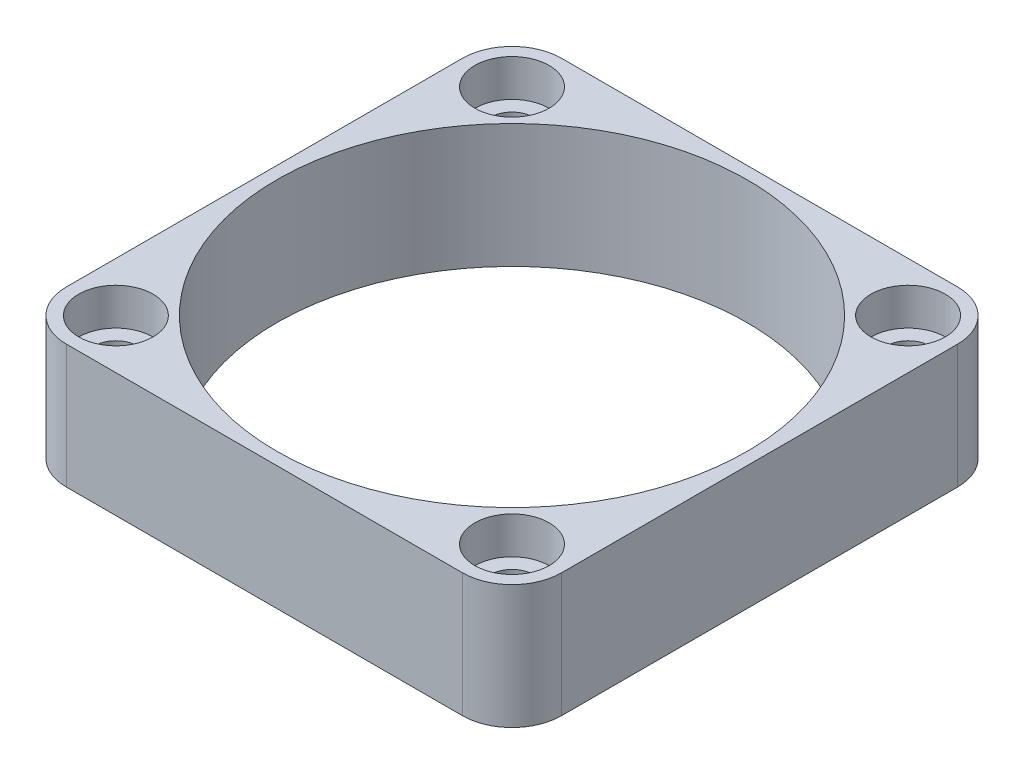
SolidWorks part; units mm, degrees
material "ABS"
ref_plane "Front Plane" through (0, 0, 0) normal (0, 0, 1) x (1, 0, 0)
ref_plane "Top Plane" through (0, 0, 0) normal (0, 1, 0) x (1, 0, 0)
ref_plane "Right Plane" through (0, 0, 0) normal (1, 0, 0) x (0, 0, -1)
sketch "Sketch1" plane through (0, 0, 0) normal (0, 1, 0) x (1, 0, 0)
  line L1 (4, 0) -> (36, 0)
  line L2 (0, 4) -> (0, 36)
  line L3 (4, 40) -> (36, 40)
  line L4 (40, 4) -> (40, 36)
  arc A0 (4, 40) -> (0, 36) centre (4, 36) ccw
  arc A1 (0, 4) -> (4, 0) centre (4, 4) ccw
  arc A2 (40, 4) -> (36, 0) centre (36, 4) cw
  arc A3 (40, 36) -> (36, 40) centre (36, 36) ccw
  point P7 (0, 40)
  point P10 (0, 0)
  point P16 (4, 36)
  point P17 (36, 36)
  point P18 (36, 4)
  point P19 (4, 4)
  dimension "D2" = 4
  dimension "D1" = 40
extrude "Boss-Extrude1" add sketch "Sketch1" along normal blind 10
sketch "Sketch2" plane through (0, 10, 0) normal (0, 1, 0) x (1, 0, 0)
  line L0 (20, 0) -> (20, 40) construction
  line L1 (4, 0) -> (36, 0) construction
  line L2 (4, 40) -> (36, 40) construction
  line L3 (0, 20) -> (40, 20) construction
  line L4 (0, 4) -> (0, 36) construction
  line L5 (40, 4) -> (40, 36) construction
  circle A0 centre (4, 4) radius 3
  circle A1 centre (4, 4) radius 1.75
  circle A2 centre (4, 36) radius 1.75
  circle A3 centre (4, 36) radius 3
  circle A4 centre (36, 4) radius 1.75
  circle A5 centre (36, 4) radius 3
  circle A6 centre (36, 36) radius 1.75
  circle A7 centre (36, 36) radius 3
  point P0 (4, 36)
  point P1 (36, 36)
  point P3 (36, 4)
  point P5 (4, 4)
  dimension "D1" = 6
  dimension "D2" = 3.5
extrude "Cut-Extrude1" cut sketch "Sketch2" against normal blind 3 contours A2 | A6 | A7 A6 | A3 A2 | A0 A1 | A1 | A5 A4 | A4 region at (1.0849, 10, -4) region at (4, 10, -4) region at (4, 10, -36) region at (1.0849, 10, -36) region at (36, 10, -4) region at (33.0849, 10, -4) region at (36, 10, -36) region at (33.0849, 10, -36)
extrude "Cut-Extrude2" cut sketch "Sketch2<5>" against normal through all contours A6 | A2 | A1 | A4 region at (4, 10, -4) region at (4, 10, -36) region at (36, 10, -36)
sketch "Sketch2<5>" plane through (0, 10, 0) normal (0, 1, 0) x (1, 0, 0) same geometry as "Sketch2"
sketch "Sketch5" plane through (0, 10, 0) normal (0, 1, 0) x (1, 0, 0)
  line L0 (20, 40) -> (20, 0) construction
  line L1 (36, 40) -> (4, 40) construction
  line L2 (4, 0) -> (36, 0) construction
  line L3 (0, 20) -> (40, 20) construction
  line L4 (0, 36) -> (0, 4) construction
  line L5 (40, 4) -> (40, 36) construction
  circle A0 centre (20, 20) radius 19
  dimension "D1" = 38
extrude "Cut-Extrude3" cut sketch "Sketch5" against normal through all
sketch "Sketch6" plane through (0, 10, 0) normal (0, 1, 0) x (1, 0, 0)
  line L0 (4, 40) -> (36, 40)
  line L1 (4, 40) -> (36, 40)
  line L2 (40, 36) -> (40, 4)
  line L3 (40, 36) -> (40, 4)
  line L4 (36, 0) -> (4, 0)
  line L5 (36, 0) -> (4, 0)
  line L6 (0, 4) -> (0, 36)
  line L7 (0, 4) -> (0, 36)
  arc A0 (40, 36) -> (36, 40) centre (36, 36) ccw
  arc A1 (40, 36) -> (36, 40) centre (36, 36) ccw
  arc A2 (36, 0) -> (40, 4) centre (36, 4) ccw
  arc A3 (36, 0) -> (40, 4) centre (36, 4) ccw
  arc A4 (0, 4) -> (4, 0) centre (4, 4) ccw
  arc A5 (0, 4) -> (4, 0) centre (4, 4) ccw
  arc A6 (4, 40) -> (0, 36) centre (4, 36) ccw
  arc A7 (4, 40) -> (0, 36) centre (4, 36) ccw
  point P12 (20, 20)
